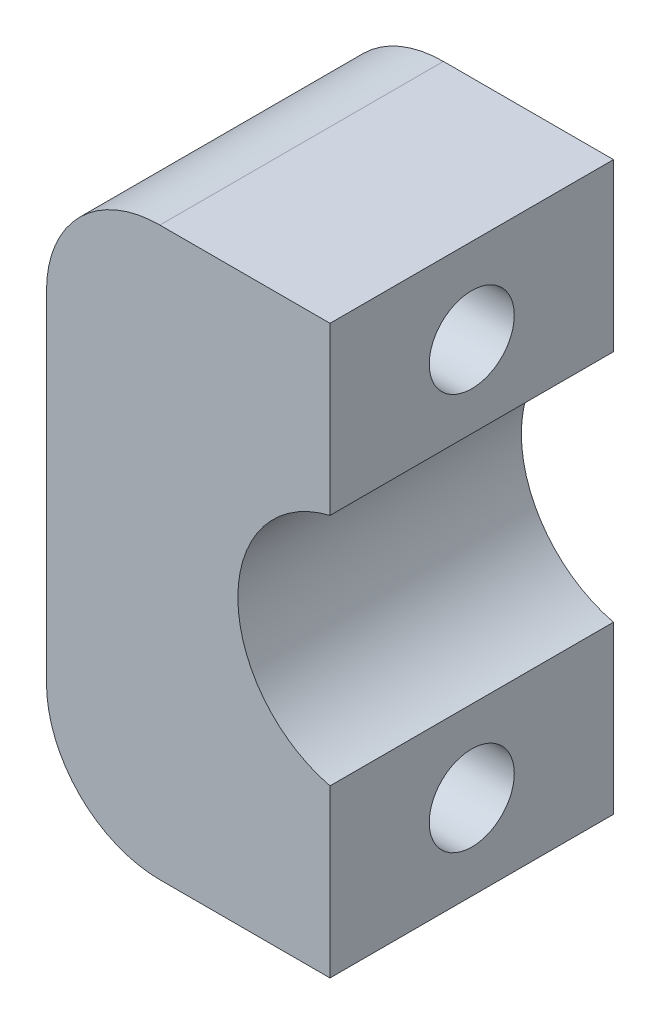
SolidWorks part; units mm, degrees
ref_plane "Front Plane" through (0, 0, 0) normal (0, 0, 1) x (1, 0, 0)
ref_plane "Top Plane" through (0, 0, 0) normal (0, 1, 0) x (1, 0, 0)
ref_plane "Right Plane" through (0, 0, 0) normal (1, 0, 0) x (0, 0, -1)
sketch "Sketch1" plane through (0, 0, 0) normal (0, 1, 0) x (1, 0, 0)
  line L1 (5, -5) -> (-5, -5)
  line L2 (5, -5) -> (5, 5)
  line L3 (5, 5) -> (-5, 5)
  line L4 (-5, -5) -> (-5, 5)
  line L5 (5, -5) -> (-5, 5) construction
  line L6 (5, 5) -> (-5, -5) construction
  point P0 (0, 0)
  dimension "D1" = 10
  dimension "D2" = 10
extrude "Boss-Extrude1" add sketch "Sketch1" along normal blind 20
sketch "Sketch2" plane through (0, 0, 5) normal (0, 0, 1) x (1, 0, 0)
  line L1 (5, 20) -> (5, 0) construction
  line L2 (-5, 20) -> (-5, 0) construction
  circle A1 centre (6, 10) radius 4.25
  point P0 (-5, 10)
  point P5 (0, 0)
  dimension "D3" = 8.5
  dimension "D1" = 1
extrude "Cut-Extrude1" cut sketch "Sketch2" against normal through all
sketch "Sketch3" plane through (5, 0, 0) normal (1, 0, 0) x (0, 0, -1)
  line L0 (-1005, 10) -> (48995, 10) construction
  line L1 (-5, 14.1307) -> (-5, 5.8693) construction
  circle A0 centre (0, 3) radius 1.5
  circle A1 centre (0, 17) radius 1.5
  point P10 (-5, 10)
  dimension "D1" = 3
  dimension "D2" = 3
  dimension "D3" = 7
  dimension "D4" = 7
extrude "Cut-Extrude2" cut sketch "Sketch3" against normal through all
fillet "Fillet1" radius 4 2 edges at (-5, 20, 0) (-5, 0, 0)
